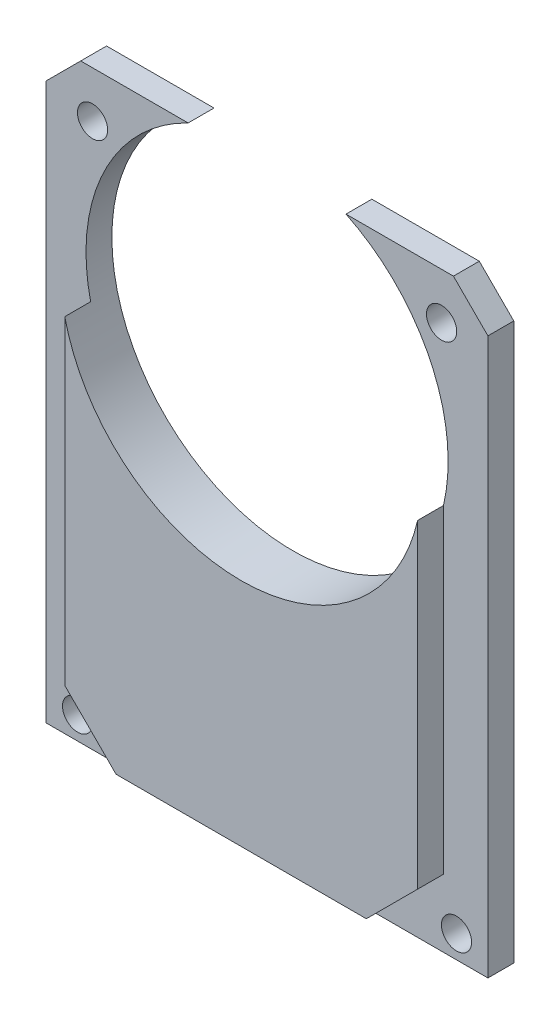
SolidWorks part; units mm, degrees
ref_plane "Front Plane" through (0, 0, 0) normal (0, 0, 1) x (1, 0, 0)
ref_plane "Top Plane" through (0, 0, 0) normal (0, 1, 0) x (1, 0, 0)
ref_plane "Right Plane" through (0, 0, 0) normal (1, 0, 0) x (0, 0, -1)
sketch "Sketch1" plane through (0, 0, 0) normal (0, 0, 1) x (1, 0, 0)
  line L1 (-25.615, -34.25) -> (25.615, -34.25)
  line L2 (-25.615, -34.25) -> (-25.615, 34.25)
  line L3 (-25.615, 34.25) -> (25.615, 34.25)
  line L4 (25.615, -34.25) -> (25.615, 34.25)
  line L5 (-25.615, -34.25) -> (25.615, 34.25) construction
  line L6 (-25.615, 34.25) -> (25.615, -34.25) construction
  point P0 (0, 0)
  dimension "D1" = 68.5
  dimension "D2" = 51.23
extrude "Boss-Extrude1" add sketch "Sketch1" along normal blind 3
chamfer "Chamfer1" distance 4 angle 45 2 edges at (25.615, 34.25, 1.5) (-25.615, 34.25, 1.5)
sketch "Sketch3" plane through (0, 0, 3) normal (0, 0, 1) x (1, 0, 0)
  line L5 (0, -34.25) -> (0, -1.6) construction
  line L6 (-25.615, -34.25) -> (25.615, -34.25) construction
  line L9 (-25.615, 30.25) -> (-25.615, -34.25) construction
  line L10 (-20.465, -32.35) -> (20.465, -32.35)
  line L11 (-20.465, -32.35) -> (-20.465, 29.15)
  line L12 (-20.465, 29.15) -> (20.465, 29.15)
  line L13 (20.465, -32.35) -> (20.465, 29.15)
  line L14 (-20.465, -32.35) -> (20.465, 29.15) construction
  line L15 (-20.465, 29.15) -> (20.465, -32.35) construction
  line L16 (25.615, -34.25) -> (25.615, 30.25) construction
  line L17 (21.615, 34.25) -> (-21.615, 34.25) construction
  point P0 (0, 0)
  dimension "D1" = 5.15
  dimension "D2" = 5.15
  dimension "D3" = 5.1
  dimension "D4" = 61.5
extrude "Boss-Extrude3" add sketch "Sketch3" along normal blind 3
chamfer "Chamfer2" distance 5.95 angle 45 4 edges at (20.465, -32.35, 4.5) (-20.465, -32.35, 4.5) (-20.465, 29.15, 4.5) (20.465, 29.15, 4.5)
sketch "Sketch4" plane through (0, 0, 3) normal (0, 0, 1) x (1, 0, 0)
  line L0 (-25.615, -34.25) -> (-21.9744, -31.605) construction
  line L1 (-25.615, -34.25) -> (25.615, -34.25) construction
  line L2 (25.615, -34.25) -> (21.9744, -31.605) construction
  line L3 (-23.615, 32.25) -> (-20.2421, 28.8771) construction
  line L4 (-21.615, 34.25) -> (-25.615, 30.25) construction
  line L5 (23.615, 32.25) -> (20.2421, 28.8771) construction
  line L6 (25.615, 30.25) -> (21.615, 34.25) construction
  circle A0 centre (-20.2421, 28.8771) radius 1.75
  circle A1 centre (20.2421, 28.8771) radius 1.75
  circle A2 centre (21.9744, -31.605) radius 1.75
  circle A3 centre (-21.9744, -31.605) radius 1.75
  dimension "D4" = 3.5
  dimension "D1" = 36
  dimension "D2" = 4.5
  dimension "D3" = 36
extrude "Cut-Extrude1" cut sketch "Sketch4" against normal through all
sketch "Sketch5" plane through (0, 0, 0) normal (0, 0, -1) x (-1, 0, 0)
  line L0 (0, -34.25) -> (0, 15.35) construction
  line L1 (25.615, -34.25) -> (-25.615, -34.25) construction
  circle A0 centre (0, 15.35) radius 21
  dimension "D1" = 42
  dimension "D2" = 49.6
extrude "Cut-Extrude2" cut sketch "Sketch5" against normal through all
ref_plane "Plane1" through (0, 0, 6) normal (0, 0, 1) x (1, 0, 0)
ref_plane "Plane2" through (-20.465, 0, 0) normal (-1, 0, 0) x (0, 0, 1)
sketch "Sketch6" plane through (-20.465, 0, 0) normal (-1, 0, 0) x (0, 0, 1)
  line L1 (6, 20.06) -> (3, 20.06)
  line L2 (6, 20.06) -> (6, 23.2)
  line L4 (3, 20.06) -> (3, 23.2)
  line L6 (3, 23.2) -> (3, 26.692)
  line L7 (3, 26.692) -> (6, 26.692)
  line L8 (6, 23.2) -> (6, 26.692)
extrude "Cut-Extrude3" cut sketch "Sketch6" against normal blind 10
ref_plane "Plane3" through (20.465, 0, 0) normal (1, 0, 0) x (0, 0, -1)
sketch "Sketch7" plane through (20.465, 0, 0) normal (1, 0, 0) x (0, 0, -1)
  line L1 (-6, 20.06) -> (-3, 20.06)
  line L2 (-6, 20.06) -> (-6, 23.2)
  line L4 (-3, 20.06) -> (-3, 23.2)
  line L6 (-6, 23.2) -> (-6, 26.5018)
  line L7 (-6, 26.5018) -> (-3, 26.5018)
  line L8 (-3, 23.2) -> (-3, 26.5018)
extrude "Cut-Extrude4" cut sketch "Sketch7" against normal blind 10
